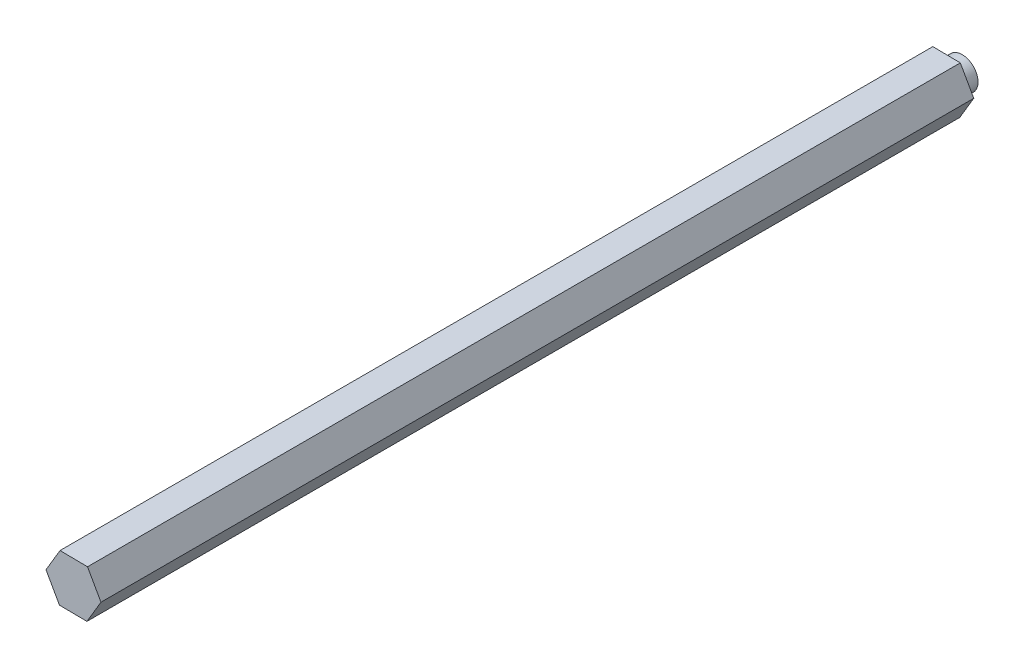
SolidWorks part; units mm, degrees
ref_plane "Front Plane" through (0, 0, 0) normal (0, 0, 1) x (1, 0, 0)
ref_plane "Top Plane" through (0, 0, 0) normal (0, 1, 0) x (1, 0, 0)
ref_plane "Right Plane" through (0, 0, 0) normal (1, 0, 0) x (0, 0, -1)
sketch "Sketch1" plane through (0, 0, 0) normal (0, 0, 1) x (1, 0, 0)
  line L1 (2.8069, 4.729) -> (-2.692, 4.7953)
  line L2 (-2.692, 4.7953) -> (-5.4989, 0.0663)
  line L3 (-5.4989, 0.0663) -> (-2.8069, -4.729)
  line L4 (-2.8069, -4.729) -> (2.692, -4.7953)
  line L5 (2.692, -4.7953) -> (5.4989, -0.0663)
  line L6 (5.4989, -0.0663) -> (2.8069, 4.729)
  circle A0 centre (0, 0) radius 4.7625 construction
  dimension "D1" = 9.525
extrude "Boss-Extrude1" add sketch "Sketch1" along normal blind 177.8
sketch "Sketch3" plane through (0, 0, 0) normal (0, 0, -1) x (-1, 0, 0)
  line L6 (-2.8069, 4.729) -> (-5.4989, -0.0663)
  line L7 (-5.4989, -0.0663) -> (-2.692, -4.7953)
  line L8 (-2.692, -4.7953) -> (2.8069, -4.729)
  line L9 (2.8069, -4.729) -> (5.4989, 0.0663)
  line L10 (5.4989, 0.0663) -> (2.692, 4.7953)
  line L11 (2.692, 4.7953) -> (-2.8069, 4.729)
  line L12 (-2.8069, 4.729) -> (-5.4989, -0.0663)
  line L13 (-5.4989, -0.0663) -> (-2.692, -4.7953)
  line L14 (-2.692, -4.7953) -> (2.8069, -4.729)
  line L15 (2.8069, -4.729) -> (5.4989, 0.0663)
  line L16 (5.4989, 0.0663) -> (2.692, 4.7953)
  line L17 (2.692, 4.7953) -> (-2.8069, 4.729)
  circle A0 centre (0, 0) radius 3.175
  dimension "D2" = 6.35
  dimension "D1" = 0
extrude "Cut-Extrude2" cut sketch "Sketch3" against normal blind 3.175
